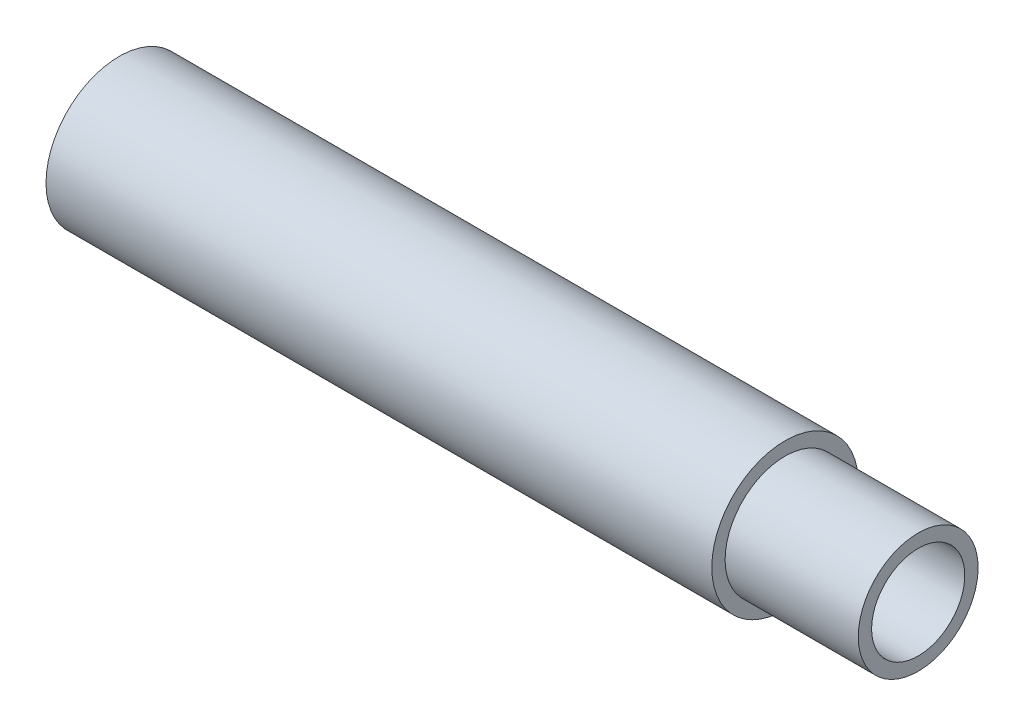
SolidWorks part; units mm, degrees
ref_plane "Front Plane" through (0, 0, 0) normal (0, 0, 1) x (1, 0, 0)
ref_plane "Top Plane" through (0, 0, 0) normal (0, 1, 0) x (1, 0, 0)
ref_plane "Right Plane" through (0, 0, 0) normal (1, 0, 0) x (0, 0, -1)
sketch "Sketch1" plane through (0, 0, 0) normal (0, 1, 0) x (1, 0, 0)
  line L0 (-13.7374, 0) -> (0, -5)
  line L1 (0, 0) -> (-250, 0)
  line L2 (0, 0) -> (0, 5)
  line L3 (0, 5) -> (-250, 5)
  line L4 (-250, 0) -> (-250, 5)
  line L5 (0, 0) -> (50, 0)
  line L6 (0, 0) -> (0, -5)
  line L7 (0, -5) -> (50, -5)
  line L8 (50, 0) -> (50, -5)
  line L9 (-13.7374, 0) -> (0, 0)
  line L10 (0, -5) -> (0, 0)
  line L11 (-250, -22.5) -> (-66.7987, -22.5)
  dimension "D1" = 250
  dimension "D2" = 5
  dimension "D3" = 5
  dimension "D4" = 50
  dimension "D5" = 160
  dimension "D6" = 22.5
revolve "Revolve1" add sketch "Sketch1" angle 360 about L11 region at (-4.5791, 0, 1.6667) region at (-125, 0, -2.5) region at (25, 0, 2.5)
